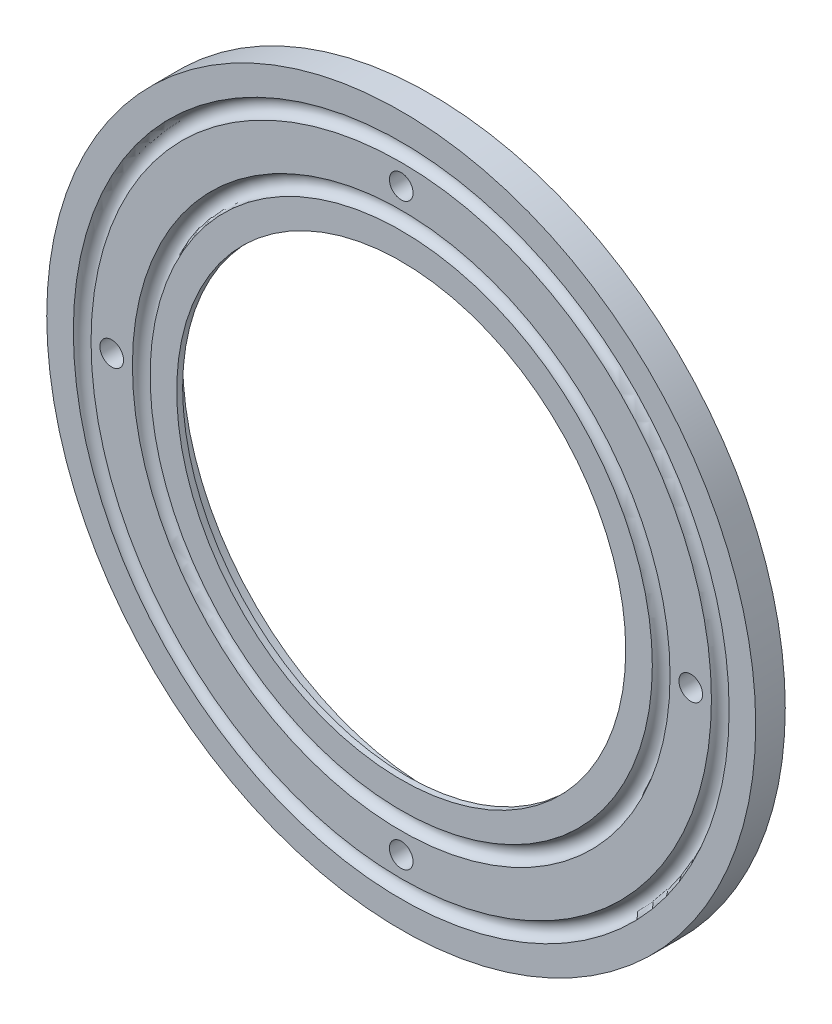
SolidWorks part; units mm, degrees
ref_plane "Front Plane" through (0, 0, 0) normal (0, 0, 1) x (1, 0, 0)
ref_plane "Top Plane" through (0, 0, 0) normal (0, 1, 0) x (1, 0, 0)
ref_plane "Right Plane" through (0, 0, 0) normal (1, 0, 0) x (0, 0, -1)
sketch "Sketch3" plane through (0, 0, 0) normal (0, 1, 0) x (1, 0, 0)
  line L0 (0, 0) -> (0, 79.4731) construction
  line L1 (0, 0) -> (38, 0) construction
  line L2 (60, 0) -> (60, 5)
  line L3 (38, 5) -> (60, 5)
  line L4 (38, 0) -> (42.5, 0)
  line L5 (45.5, 0) -> (52.5, 0)
  line L6 (38, 0) -> (38, 5)
  line L7 (55.5, 0) -> (60, 0)
  line L8 (38, 5) -> (0, 5) construction
  arc A0 (45.5, 0) -> (42.5, 0) centre (44, 0) ccw
  arc A1 (55.5, 0) -> (52.5, 0) centre (54, 0) ccw
  point P6 (0, 0)
  point P15 (0, 0)
  dimension "D5" = 6
  dimension "D6" = 5
  dimension "D2" = 6
  dimension "D1" = 60
  dimension "D3" = 44
  dimension "D4" = 54
  dimension "D7" = 38
  dimension "D8" = 5
  dimension "D10" = 6
revolve "Revolve1" add sketch "Sketch3" angle 360 about L0
sketch "Sketch4" plane through (0, 0, 0) normal (0, 0, 1) x (1, 0, 0)
  circle A0 centre (0, 0) radius 52.5 construction
  circle A1 centre (0, 0) radius 45.5 construction
  circle A2 centre (0, 0) radius 49 construction
  circle A3 centre (49, 0) radius 2
  circle A4 centre (-49, 0) radius 2
  circle A5 centre (0, 49) radius 2
  circle A6 centre (0, -49) radius 2
  dimension "D1" = 7
  dimension "D2" = 98
  dimension "D3" = 4
  dimension "D4" = 4
  dimension "D5" = 4
  dimension "D6" = 4
extrude "Cut-Extrude1" cut sketch "Sketch4" against normal blind 10
sketch "Sketch5" plane through (0, 0, -5) normal (0, 0, -1) x (-1, 0, 0)
  circle A2 centre (0, 0) radius 38
  circle A3 centre (0, 0) radius 42
  dimension "D1" = 76
  dimension "D2" = 84
extrude "Cut-Extrude2" cut sketch "Sketch5" against normal blind 4 contours A3
